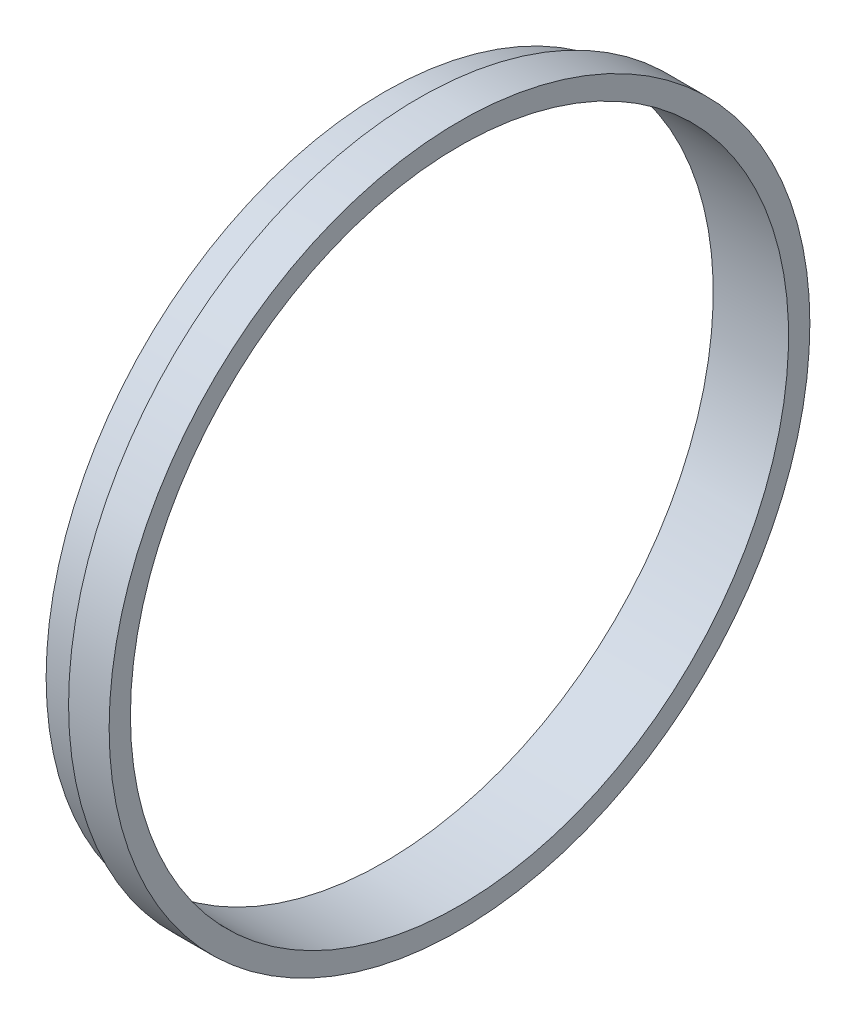
SolidWorks part; units mm, degrees
material "Stiffener Ring"
ref_plane "Front Plane" through (0, 0, 0) normal (0, 0, 1) x (1, 0, 0)
ref_plane "Top Plane" through (0, 0, 0) normal (0, 1, 0) x (1, 0, 0)
ref_plane "Right Plane" through (0, 0, 0) normal (1, 0, 0) x (0, 0, -1)
sketch "OuterDiameter" plane through (0, 0, 0) normal (1, 0, 0) x (0, 0, -1)
  circle A0 centre (0, 0) radius 154.627
  circle A1 centre (0, 0) radius 145.227
  dimension "D1" = 290.454
  dimension "D2" = 9.4
ref_axis "Axis3" through (-72.365, 0, 0) along (1, 0, 0)
sketch "Sketch2" plane through (0, 0, 0) normal (0, 0, 1) x (1, 0, 0)
  line L0 (0, 145.227) -> (33.25, 145.227)
  line L1 (33.25, 145.227) -> (33.25, 154.627)
  line L2 (33.25, 154.627) -> (15.35, 154.627)
  line L3 (15.35, 154.627) -> (15.35, 151.902)
  line L4 (15.35, 151.902) -> (20.15, 151.902)
  line L5 (20.15, 151.902) -> (20.15, 149.177)
  line L6 (20.15, 149.177) -> (0, 149.177)
  line L7 (0, 149.177) -> (0, 145.227)
  dimension "D1" = 3.95
  dimension "D2" = 2.725
  dimension "D3" = 9.4
  dimension "D4" = 20.15
  dimension "D5" = 33.25
  dimension "D6" = 17.9
  dimension "D7" = 145.227
revolve "Revolve1" add sketch "Sketch2" angle 360 about axis through (-72.365, 0, 0) along (1, 0, 0)
